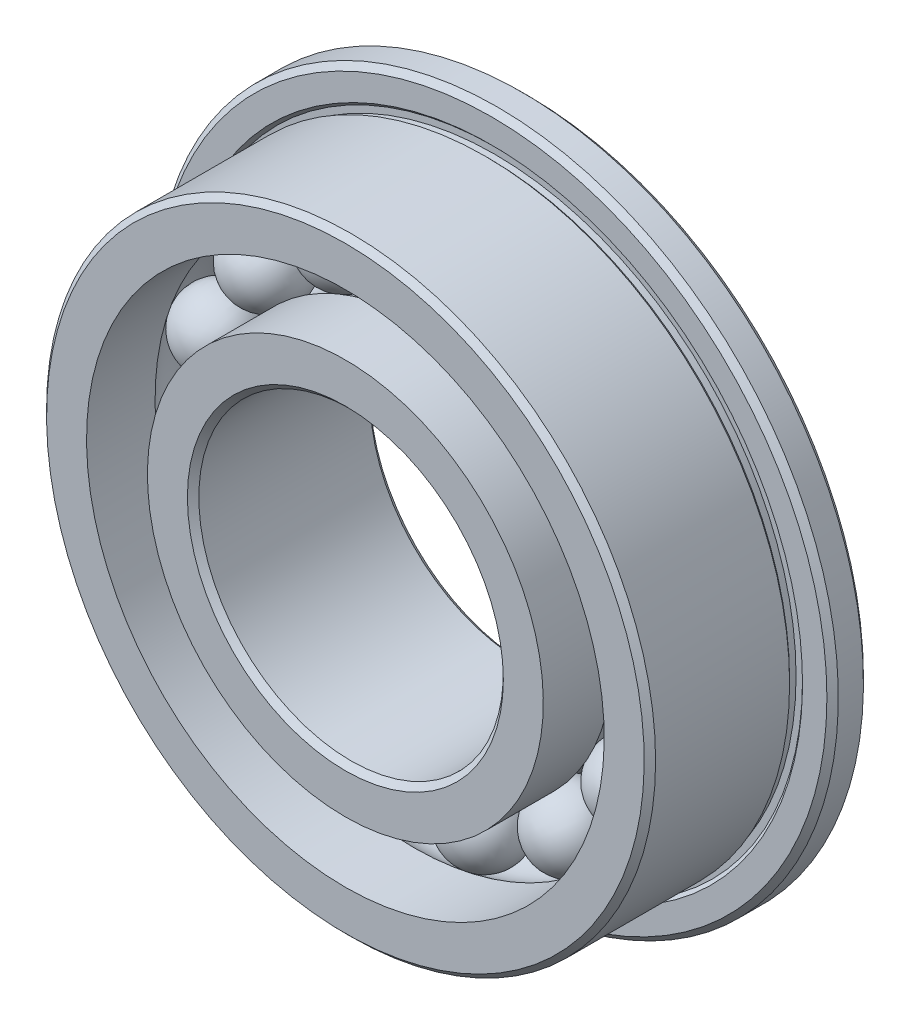
SolidWorks part; units mm, degrees
ref_plane "Front Plane" through (0, 0, 0) normal (0, 0, 1) x (1, 0, 0)
ref_plane "Top Plane" through (0, 0, 0) normal (0, 1, 0) x (1, 0, 0)
ref_plane "Right Plane" through (0, 0, 0) normal (1, 0, 0) x (0, 0, -1)
sketch "Sketch1" plane through (0, 0, 0) normal (1, 0, 0) x (0, 0, -1)
  line L0 (0, 5) -> (0, -5) construction
  line L1 (-1.5, 5) -> (1.5, 5) construction
  line L2 (0, 0) -> (1.5, 0) construction
  line L3 (1.5, 5.6) -> (1.5, -5.6) construction
  line L4 (1.5, -5.6) -> (0.9, -5.6) construction
  line L5 (1.5, 2.5) -> (0, 2.5) construction
  line L6 (1.5, 2.5) -> (1.5, -2.5) construction
  dimension "OD" = 10
  dimension "Width" = 3
  dimension "Flange Thickness" = 0.6
  dimension "ID" = 5
  dimension "Flange OD" = 11.2
sketch "Sketch2" plane through (0, 0, 0) normal (1, 0, 0) x (0, 0, -1)
  line L0 (1.5, 5.6) -> (0.9, 5.6)
  line L1 (0.9, 5.6) -> (0.9, 5.1061)
  line L2 (0.7939, 5) -> (-1.5, 5)
  line L3 (-1.5, 5) -> (-1.5, 4.25)
  line L4 (-1.5, 4.25) -> (-0.375, 4.25)
  line L5 (1.5, 5.6) -> (1.5, -5.6) construction
  line L6 (1.5, 4.25) -> (1.5, 5.6)
  line L7 (1.5, 2.5) -> (-1.5, 2.5)
  line L8 (-1.5, 2.5) -> (-1.5, 3.25)
  line L9 (-1.5, 3.25) -> (-0.375, 3.25)
  line L10 (1.5, 3.25) -> (1.5, 2.5)
  line L11 (0, 5) -> (0, 2.5) construction
  line L12 (-0.625, 3.75) -> (0.625, 3.75) construction
  line L13 (0.375, 4.25) -> (1.5, 4.25)
  line L14 (0.375, 3.25) -> (1.5, 3.25)
  line L15 (0.9, 5.1061) -> (0.953, 5.053)
  line L16 (0.953, 5.053) -> (0.953, 4.947)
  line L17 (0.953, 4.947) -> (0.847, 4.947)
  line L18 (0.847, 4.947) -> (0.7939, 5)
  line L19 (0.9, 5) -> (0.953, 4.947) construction
  line L20 (0.953, 5.053) -> (0.847, 4.947) construction
  line L21 (0.7939, 5) -> (0.9, 5) construction
  line L22 (0.9, 5) -> (0.9, 5.1061) construction
  circle A0 centre (0, 3.75) radius 0.625 construction
  arc A1 (-0.375, 4.25) -> (0.375, 4.25) centre (0, 3.75) cw
  arc A2 (-0.375, 3.25) -> (0.375, 3.25) centre (0, 3.75) ccw
  dimension "D1" = 2.5
  dimension "Ball Dia." = 1.25
  dimension "D2" = 135
  dimension "D3" = 0.15
  dimension "D4" = 1
  dimension "Race Thikness" = 0.75
revolve "Revolve1" add sketch "Sketch2" angle 360 about L2
fillet "Fillet1" radius 0.0938 3 edges at (0, -5.6, -1.5) (0, -5.6, -0.9) (0, -5, 1.5) profile chamfer
sketch "Sketch3" plane through (0, 0, 0) normal (0, 0, 1) x (1, 0, 0)
  line L0 (-2.5, 0) -> (2.5, 0) construction
  line L1 (-5, 0) -> (5, 0) construction
  point P5 (0, 0)
  dimension "ID2" = 5
  dimension "OD2" = 10
fillet "Fillet2" radius 0.0938 2 edges at (0, -2.5, -1.5) (0, -2.5, 1.5) profile chamfer
sketch "Sketch7" plane through (0, 0, 0) normal (0, 0, 1) x (1, 0, 0)
  line L0 (0, 4.375) -> (0, 3.125)
  line L1 (0, 5.6) -> (0, -5.6) construction
  line L2 (-0.7395, 4.375) -> (0, 0) construction
  line L3 (0, 0) -> (0.7395, 4.375) construction
  line L4 (0.7395, 4.375) -> (-0.7395, 4.375) construction
  circle A0 centre (0, 3.75) radius 0.625 construction
  circle A1 centre (0, 0) radius 4.375 construction
  circle A2 centre (0, 0) radius 3.125 construction
  arc A4 (0, 4.375) -> (0, 3.125) centre (0, 3.75) ccw
  dimension "D1" = 19.188
revolve "Revolve3" add sketch "Sketch7" angle 360 about L0
pattern_circular "CirPattern3" count 15 over 360 about axis through (0, 0, 0) along (0, 0, -1) of bodies 107
sketch "Sketch8" plane through (0, 0, 0) normal (1, 0, 0) x (0, 0, -1)
  line L0 (-1.5, 5) -> (1.5, 5) construction
  line L1 (1.5, 5) -> (1.5, 5.6) construction
  line L2 (-1.5, -5) -> (1.5, -5) construction
  line L3 (1.5, 5.6) -> (1.5, -5.6) construction
  dimension "D1" = 10
equation "\"Ball Dia.@Sketch2\" = ( \"OD@Sketch1\" - \"ID@Sketch1\" ) * .25"
equation "\"D3@Sketch2\"=\"Flange Thickness@Sketch1\"/4"
equation "\"D1@Fillet1\" = \"Race Thikness@Sketch2\" / 8"
equation "\"ID2@Sketch3\" = \"ID@Sketch1\""
equation "\"OD2@Sketch3\" = \"OD@Sketch1\""
equation "\"D1@Fillet2\" = \"Race Thikness@Sketch2\" / 8"
equation "\"D1@CirPattern3\"=360/\"D1@Sketch7\"-4"
equation "\"D4@Sketch2\" = ( \"OD@Sketch1\" - \"ID@Sketch1\" ) * .2"
